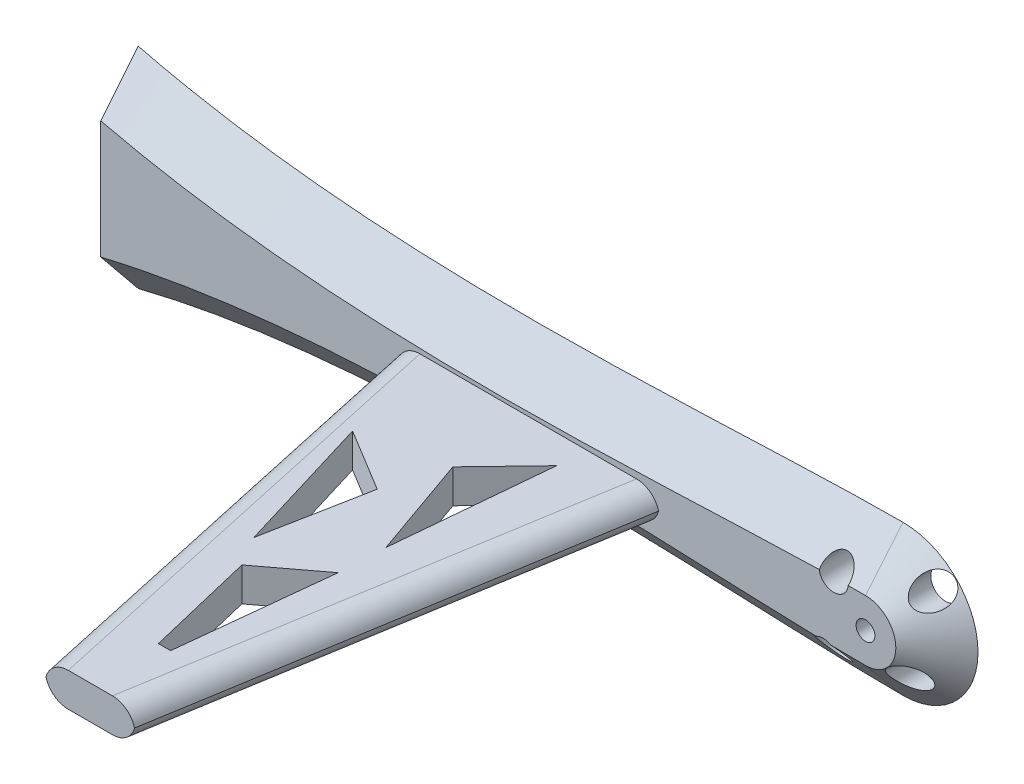
SolidWorks part; units mm, degrees
ref_plane "Front Plane" through (0, 0, 0) normal (0, 0, 1) x (1, 0, 0)
ref_plane "Top Plane" through (0, 0, 0) normal (0, 1, 0) x (1, 0, 0)
ref_plane "Right Plane" through (0, 0, 0) normal (1, 0, 0) x (0, 0, -1)
sketch "Sketch3" plane through (0, 0, 0) normal (0, 0, 1) x (1, 0, 0)
  line L0 (-150, 0) -> (0, 0) construction
  line L1 (0, 0) -> (150, 0) construction
  line L2 (0, 0) -> (0, -150) construction
  line L3 (0, 0) -> (0, 150) construction
  line L4 (50, 0) -> (0, 50) construction
  line L5 (0, 50) -> (-16.1612, 33.8388) construction
  line L6 (-50, 0) -> (0, -50) construction
  line L7 (0, -50) -> (50, 0) construction
  line L10 (-150, -10) -> (-130, -10) construction
  line L11 (-10, -150) -> (-10, -140) construction
  line L12 (-144.3431, 5.6569) -> (-155.6569, -5.6569) construction
  line L13 (-154.2426, 4.2426) -> (-145.7574, -4.2426) construction
  line L14 (-136, 0) -> (-101, 0) construction
  line L17 (1.6, -42.5) -> (-1.6, -32.5) construction
  line L30 (-136, 0) -> (-50, 0) construction
  line L151 (-37.5, 0) -> (-14, 0) construction
  line L152 (-37.5, 0) -> (-14, 0) construction
  line L174 (10.6066, 31.8198) -> (31.8198, 10.6066) construction
  line L178 (0, -130) -> (0, -37.5) construction
  line L184 (0, -84.6854) -> (-9.8172, -84.6854) construction
  line L212 (-1.6, -82.1854) -> (1.6, -87.1854) construction
  line L213 (-1.6, -87.1854) -> (1.6, -82.1854) construction
  line L225 (0, 0) -> (21.2132, 21.2132) construction
  line L226 (0, 0) -> (7.7782, 7.7782) construction
  line L227 (13.0815, 2.4749) -> (2.4749, 13.0815) construction
  line L228 (2.4749, 13.0815) -> (-13.0815, -2.4749) construction
  line L229 (-13.0815, -2.4749) -> (-2.4749, -13.0815) construction
  line L230 (-2.4749, -13.0815) -> (13.0815, 2.4749) construction
  line L231 (48, -14) -> (48, 14)
  line L232 (25, 25) -> (48, 14) construction
  line L235 (14, -48) -> (48, -14) construction
  line L236 (-48, 14) -> (-14, 48) construction
  line L237 (-33.8388, 16.1612) -> (-50, 0) construction
  arc A0 (-10, -150) -> (10, -150) centre (0, -150) ccw construction
  arc A1 (-150, 10) -> (-150, -10) centre (-150, 0) ccw construction
  arc A2 (10, 150) -> (-10, 150) centre (0, 150) ccw construction
  arc A3 (150, -10) -> (150, 10) centre (150, 0) ccw
  circle A5 centre (-155.6569, -5.6569) radius 1 construction
  circle A6 centre (-144.3431, 5.6569) radius 1 construction
  circle A7 centre (-145.7574, -4.2426) radius 1 construction
  circle A8 centre (-154.2426, 4.2426) radius 1 construction
  circle A9 centre (-5.6569, 155.6569) radius 1 construction
  circle A10 centre (-4.2426, 145.7574) radius 1 construction
  circle A11 centre (5.6569, 144.3431) radius 1 construction
  circle A12 centre (4.2426, 154.2426) radius 1 construction
  circle A13 centre (155.6569, 5.6569) radius 1
  circle A14 centre (145.7574, 4.2426) radius 1
  circle A15 centre (144.3431, -5.6569) radius 1
  circle A16 centre (154.2426, -4.2426) radius 1
  circle A17 centre (5.6569, -155.6569) radius 1 construction
  circle A18 centre (4.2426, -145.7574) radius 1 construction
  circle A19 centre (-5.6569, -144.3431) radius 1 construction
  circle A20 centre (-4.2426, -154.2426) radius 1 construction
  circle A25 centre (-150, 0) radius 3.5 construction
  circle A26 centre (0, 150) radius 3.5 construction
  circle A27 centre (150, 0) radius 3.5
  circle A28 centre (0, -150) radius 3.5 construction
  circle A29 centre (0, 0) radius 37.5 construction
  circle A30 centre (0, 0) radius 2.5 construction
  spline S0 degree 3 poles (-10, -150) (-10, -125.1194) (-3.9823, -72.8858) (-22.3124, -22.3138) (-72.8976, -3.9806) (-125.0121, -10) (-150, -10) knots 0 0 0 0 0.361155 0.451427 0.541698 0.902854 0.902854 0.902854 0.902854 construction
  spline S1 degree 3 poles (-150, 10) (-125.1194, 10) (-83.3309, 5.1856) (-48, 14) knots 0 0 0 0 0.361155 0.361155 0.361155 0.361155 construction
  spline S2 degree 3 poles (10, 150) (10, 125.1194) (3.9823, 72.8858) (20.3008, 27.8639) (29.2345, 21.3926) (31.7306, 19.9855) knots 0 0 0 0 0.361155 0.451427 0.482249 0.482249 0.482249 0.482249 construction
  spline S3 degree 3 poles (150, -10) (125.1194, -10) (83.3309, -5.1856) (48, -14) knots 0 0 0 0 0.361155 0.361155 0.361155 0.361155
  spline S4 degree 3 poles (14, -48) (5.1843, -83.3189) (10, -125.0121) (10, -150) knots 0.541698 0.541698 0.541698 0.541698 0.902854 0.902854 0.902854 0.902854 construction
  spline S5 degree 3 poles (-14, 48) (-5.1843, 83.3189) (-10, 125.0121) (-10, 150) knots 0.541698 0.541698 0.541698 0.541698 0.902854 0.902854 0.902854 0.902854 construction
  spline S6 degree 3 poles (48, 14) (83.3189, 5.1843) (125.0121, 10) (150, 10) knots 0.541698 0.541698 0.541698 0.541698 0.902854 0.902854 0.902854 0.902854
  point P2 (0, -37.5)
  point P14 (-150, 0)
  point P16 (0, 0)
  point P27 (-150, 0)
  point P46 (0, 0)
  point P77 (0, 0)
  point P78 (0, -37.5)
  point P88 (-118.5, 0)
  point P95 (0, 0)
  point P116 (-93, 0)
  point P118 (0, 0)
  point P138 (0, 0)
  point P141 (7.7782, 7.7782)
  point P221 (0, 0)
  point P228 (0, 0)
  point P229 (-25.75, 0)
  point P249 (0, 0)
  point P254 (21.2132, 21.2132)
  point P448 (0, 0)
  dimension "D2" = 20
  dimension "D3" = 4
  dimension "D9" = 2
  dimension "D14" = 7
  dimension "D16" = 75
  dimension "D21" = 5
  dimension "D24" = 15
  dimension "D13" = 0
  dimension "D1" = 300
  dimension "D5" = 20
  dimension "D6" = 10
  dimension "D7" = 16
  dimension "D8" = 12
  dimension "D11" = 35
  dimension "D18" = 5
  dimension "D19" = 3.2
  dimension "D22" = 11
  dimension "D23" = 30
  dimension "D25" = 22
  dimension "D10" = 4
  dimension "D15" = 4
sketch "Sketch5" plane through (0, 0, 0) normal (0, 0, 1) x (1, 0, 0)
  line L0 (48, 0) -> (160, 0) construction
  line L1 (48, 14) -> (48, -14)
  line L2 (48, 14) -> (48, -14)
  line L3 (48, 2.5) -> (48, -2.5)
  line L4 (48, 2.5) -> (159.6825, 2.5) construction
  line L5 (48, -2.5) -> (159.6825, -2.5) construction
  line L6 (48, 0) -> (160, 0)
  arc A0 (159.6825, -2.5) -> (150, 10) centre (150, 0) ccw
  arc A1 (150, -10) -> (150, 10) centre (150, 0) ccw
  arc A2 (150, -10) -> (150, 10) centre (150, 0) ccw construction
  circle A3 centre (154.2426, -4.2426) radius 1
  circle A4 centre (154.2426, -4.2426) radius 1 construction
  circle A5 centre (144.3431, -5.6569) radius 1
  circle A6 centre (144.3431, -5.6569) radius 1 construction
  circle A7 centre (145.7574, 4.2426) radius 1
  circle A8 centre (145.7574, 4.2426) radius 1 construction
  circle A9 centre (155.6569, 5.6569) radius 1
  circle A10 centre (155.6569, 5.6569) radius 1 construction
  circle A11 centre (150, 0) radius 3.5
  circle A12 centre (150, 0) radius 3.5 construction
  spline S2 degree 3 poles (-3112.6685, -2303.2) (3812.7181, 2585.7681) (-3347.301, -2832.8759) (2523.3414, 3114.023) knots -1.176452 -1.176452 -1.176452 -1.176452 2.634432 2.634432 2.634432 2.634432 only from (150, 10) to (48, 14)
  spline S3 degree 3 poles (2544.439, -3097.4273) (-3366.1997, 2813.8933) (3828.943, -2565.011) (-3127.9981, 2281.2783) knots -1.728165 -1.728165 -1.728165 -1.728165 2.073728 2.073728 2.073728 2.073728 only from (48, -14) to (150, -10)
  spline S4 degree 3 poles (150, 10) (125.0121, 10) (83.3189, 5.1843) (48, 14) knots 0.541698 0.541698 0.541698 0.541698 0.902854 0.902854 0.902854 0.902854
  spline S5 degree 3 poles (48, -14) (83.3309, -5.1856) (125.1194, -10) (150, -10) knots 0 0 0 0 0.361155 0.361155 0.361155 0.361155 construction
  point P25 (48, 0)
  dimension "D7" = 5
  dimension "D1" = 0
  dimension "D2" = 0
  dimension "D3" = 0
  dimension "D4" = 0
  dimension "D5" = 0
  dimension "D6" = 0
extrude "Boss-Extrude2" add sketch "Sketch5" along normal blind 5 contours A0 S4 L2 L5
mirror "Mirror5" about plane through (0, 0, 5) normal (0, 1, 0) of "Boss-Extrude2"
chamfer "Chamfer6" distance 5 angle 50 3 edges at (160, 0, 5)
sketch "Sketch6" plane through (0, 0, 0) normal (0, 0, -1) x (-1, 0, 0)
  line L0 (-150, 10) -> (-150, -10) construction
  line L1 (-160, 0) -> (-150, 0) construction
  line L2 (-150, 0) -> (-141.1756, 0) construction
  line L3 (-145.7557, 4.2341) -> (-150, 0) construction
  line L4 (-150, 0) -> (-154.241, -4.2512) construction
  line L5 (-144.3415, -5.6654) -> (-149.9983, -0.0085) construction
  line L6 (-149.9983, -0.0085) -> (-155.6552, 5.6483) construction
  arc A0 (-150, 10) -> (-150, -10) centre (-150, 0) ccw construction
  arc A1 (-150.0085, -10.0017) -> (-150.0085, 9.9983) centre (-150.0085, -0.0017) ccw construction
  circle A2 centre (-155.6552, 5.6483) radius 1.95
  circle A3 centre (-154.241, -4.2512) radius 1.95
  circle A4 centre (-144.3415, -5.6654) radius 1.95
  circle A5 centre (-145.7557, 4.2341) radius 1.95
  circle A6 centre (-149.9983, -0.0085) radius 1.25
  dimension "D1" = 3.9
  dimension "D2" = 2.5
extrude "Cut-Extrude1" cut sketch "Sketch6" against normal through all
sketch "Sketch7" plane through (0, 0, 5) normal (0, 0, 1) x (1, 0, 0)
  line L0 (149.9983, -0.0085) -> (59.9983, -0.0085) construction
  line L2 (122.4983, -2.2585) -> (87.4983, -2.2585)
  line L3 (122.4983, -2.2585) -> (122.4983, 2.2415)
  line L4 (122.4983, 2.2415) -> (87.4983, 2.2415)
  line L5 (87.4983, -2.2585) -> (87.4983, 2.2415)
  line L6 (122.4983, -2.2585) -> (87.4983, 2.2415) construction
  line L7 (122.4983, 2.2415) -> (87.4983, -2.2585) construction
  point P3 (104.9983, -0.0085)
  dimension "D1" = 90
  dimension "D2" = 35
  dimension "D3" = 4.5
extrude "Boss-Extrude3" add sketch "Sketch7" along normal blind 70
sketch "Sketch8" plane through (0, 2.2415, 0) normal (0, 1, 0) x (1, 0, 0)
  line L1 (112.6064, -8.7946) -> (105.8227, -15.8544)
  line L2 (100.6064, -65) -> (112.6064, -65) construction
  line L3 (105.8227, -15.8544) -> (110.6754, -29.6359)
  line L4 (100.6064, -65) -> (87.4983, -5) construction
  line L5 (110.6754, -29.6359) -> (112.6064, -8.7946)
  line L6 (106.5981, -55.9063) -> (108.2287, -55.9063)
  line L7 (112.6064, -65) -> (122.4983, -5)
  line L8 (87.4983, -5) -> (122.4983, -5) construction
  line L13 (108.2287, -55.9063) -> (110.3969, -35.7268) construction
  line L20 (103.0821, -41.2527) -> (110.3969, -35.7268)
  line L21 (110.3969, -35.7268) -> (108.2287, -55.9063)
  line L22 (106.5981, -55.9063) -> (103.0821, -41.2527)
  line L24 (87.4983, -5) -> (100.6064, -65)
  line L25 (100.6064, -65) -> (112.6064, -65)
  line L27 (122.4983, -5) -> (122.4983, -75)
  line L28 (122.4983, -75) -> (87.4983, -75)
  line L29 (87.4983, -75) -> (87.4983, -5)
  line L39 (100.7105, -37.2959) -> (103.3555, -23.4789)
  line L40 (103.3555, -23.4789) -> (94.9957, -18.4051)
  line L41 (94.9957, -18.4051) -> (100.7105, -37.2959)
  dimension "D1" = 60
  dimension "D2" = 12
extrude "Cut-Extrude2" cut sketch "Sketch8" against normal through all
fillet "Fillet5" radius 3 4 edges at (94.0523, -2.2585, 35) (94.0523, 2.2415, 35) (117.5523, 2.2415, 35) (117.5523, -2.2585, 35)
